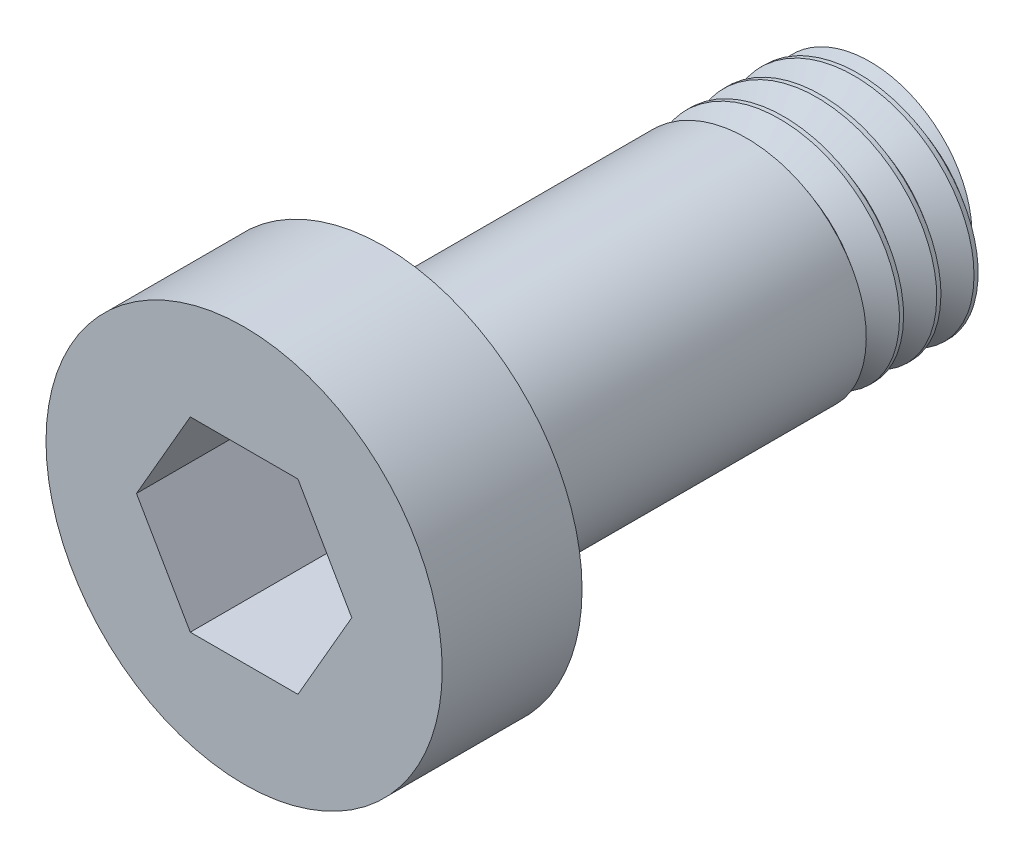
SolidWorks part; units mm, degrees
material "AISI 304"
ref_plane "Alzado" through (0, 0, 0) normal (0, 0, 1) x (1, 0, 0)
ref_plane "Planta" through (0, 0, 0) normal (0, 1, 0) x (1, 0, 0)
ref_plane "Vista lateral" through (0, 0, 0) normal (1, 0, 0) x (0, 0, -1)
ref_plane "Plano2" through (0, 0, -4.4) normal (0, 0, 1) x (1, 0, 0)
sketch "Sk_Cana" plane through (0, 0, -4.4) normal (0, 0, 1) x (1, 0, 0)
  circle A0 centre (0, 0) radius 2.5
extrude "Cana" add sketch "Sk_Cana" along normal blind 10.6
ref_plane "Plano3" through (0, 0, 6.2) normal (0, 0, 1) x (1, 0, 0)
sketch "Sk_Cabeza" plane through (0, 0, 6.2) normal (0, 0, 1) x (1, 0, 0)
  line L0 (2.3094, 0) -> (1.1547, 2)
  line L1 (1.1547, 2) -> (-1.1547, 2)
  line L2 (-1.1547, 2) -> (-2.3094, 0)
  line L3 (-2.3094, 0) -> (-1.1547, -2)
  line L4 (-1.1547, -2) -> (1.1547, -2)
  line L5 (1.1547, -2) -> (2.3094, 0)
  circle A0 centre (0, 0) radius 4.25
extrude "Cabeza" add sketch "Sk_Cabeza" along normal blind 3
ref_plane "Plano5" through (0, 0, -4.4) normal (0, 0, 1) x (1, 0, 0)
sketch "Sk_Helice_Rosca_M5x0_8" plane through (0, 0, -4.4) normal (0, 0, 1) x (1, 0, 0)
  circle A0 centre (0, 0) radius 2.5
curve "Helice_Rosca_M5x0_8" pitch 0.8 height 3 radius 2.5 centre (0, 0, -4.4) axis (0, 0, 1) start towards (1, 0, 0)
sketch "Sk_perfil_Rosca_M5x0_8" plane through (0, 0, 0) normal (0, 1, 0) x (1, 0, 0)
  line L0 (2.8, 4.9732) -> (2.8, 3.8268)
  line L1 (2.8, 3.8268) -> (2.0093, 4.4)
  line L2 (2.0093, 4.4) -> (2.8, 4.9732)
sweep "Rosca_M5x0_8" cut profiles "Sk_perfil_Rosca_M5x0_8" path "Helice_Rosca_M5x0_8" align with end faces yes
